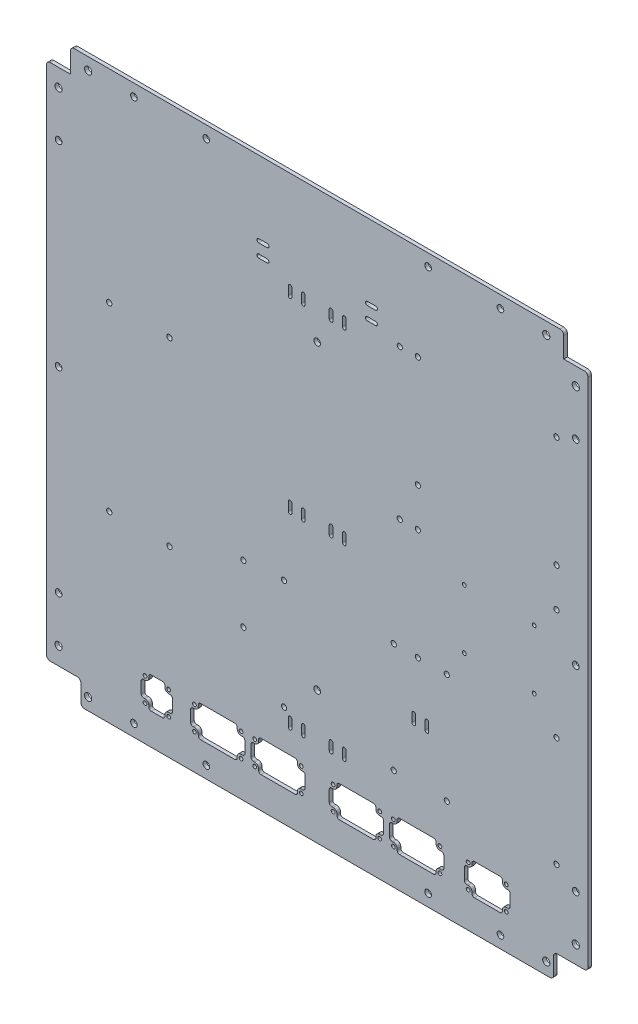
SolidWorks part; units mm, degrees
material "Acrylic (Medium-high impact)"
ref_plane "Front" through (0, 0, 0) normal (0, 0, 1) x (1, 0, 0)
ref_plane "Top" through (0, 0, 0) normal (0, 1, 0) x (1, 0, 0)
ref_plane "Right" through (0, 0, 0) normal (1, 0, 0) x (0, 0, -1)
sketch "Sketch2" plane through (0, 0, 0) normal (0, 0, 1) x (1, 0, 0)
  line L1 (0, 0) -> (449, 0)
  line L2 (0, 0) -> (0, 470)
  line L3 (0, 470) -> (449, 470)
  line L4 (449, 0) -> (449, 470)
  dimension "D1" = 449
  dimension "D2" = 470
extrude "Boss-Extrude1" add sketch "Sketch2" along normal blind 3
sketch "Sketch3" plane through (0, 0, 0) normal (0, 0, -1) x (-1, 0, 0)
  line L0 (-98.15, 52) -> (-98.15, 45.65)
  line L1 (-449, 0) -> (-429, 0)
  line L2 (-449, 0) -> (-449, 20)
  line L3 (-449, 20) -> (-429, 20)
  line L4 (-429, 0) -> (-429, 20)
  line L5 (0, 0) -> (-20, 0)
  line L6 (0, 0) -> (0, 20)
  line L7 (0, 20) -> (-20, 20)
  line L8 (-20, 0) -> (-20, 20)
  line L9 (-449, 470) -> (-429, 470)
  line L10 (-449, 470) -> (-449, 450)
  line L11 (-449, 450) -> (-429, 450)
  line L12 (-429, 470) -> (-429, 450)
  line L13 (0, 470) -> (-20, 470)
  line L14 (0, 470) -> (0, 450)
  line L15 (0, 450) -> (-20, 450)
  line L16 (-20, 470) -> (-20, 450)
  line L17 (-104.5, 26) -> (-78.5, 26) construction
  line L18 (-104.5, 26) -> (-104.5, 52) construction
  line L19 (-104.5, 52) -> (-78.5, 52) construction
  line L20 (-78.5, 26) -> (-78.5, 52) construction
  line L21 (0, 0) -> (-449, 0) construction
  line L22 (0, 470) -> (0, 0) construction
  line L23 (-98.15, 45.65) -> (-104.5, 45.65)
  line L24 (-104.5, 45.65) -> (-104.5, 32.35)
  line L25 (-104.5, 32.35) -> (-98.15, 32.35)
  line L26 (-98.15, 32.35) -> (-98.15, 26)
  line L27 (-98.15, 26) -> (-84.85, 26)
  line L28 (-84.85, 26) -> (-84.85, 32.35)
  line L29 (-84.85, 32.35) -> (-78.5, 32.35)
  line L30 (-78.5, 32.35) -> (-78.5, 45.65)
  line L31 (-78.5, 45.65) -> (-84.85, 45.65)
  line L32 (-84.85, 45.65) -> (-84.85, 52)
  line L33 (-84.85, 52) -> (-98.15, 52)
  dimension "D1" = 20
  dimension "D2" = 20
  dimension "D3" = 20
  dimension "D4" = 20
  dimension "D5" = 26
  dimension "D6" = 26
  dimension "D8" = 26
  dimension "D7" = 78.5
  dimension "D9" = 6.35
extrude "bed heater panel cutout" cut sketch "Sketch3" against normal blind 30
hole_wizard "M5 Clearance Hole1" positions "Sketch4" profile "Sketch5" hole size "M5" standard "ANSI Metric" end condition up to next
sketch "Sketch4" plane through (0, 0, 0) normal (0, 0, -1) x (-1, 0, 0)
  line L0 (-224.5, 470) -> (-224.5, 0) construction
  line L1 (-429, 470) -> (-20, 470) construction
  line L2 (-20, 0) -> (-429, 0) construction
  line L3 (-429, 460) -> (-376.5, 460) construction
  line L5 (-429, 450) -> (-429, 470) construction
  line L6 (-376.5, 460) -> (-72.5, 460) construction
  line L7 (-72.5, 460) -> (-20, 460) construction
  line L8 (-20, 470) -> (-20, 450) construction
  line L9 (-449, 235) -> (0, 235) construction
  line L10 (-449, 20) -> (-449, 450) construction
  line L12 (0, 450) -> (0, 20) construction
  line L13 (-439, 450) -> (-439, 20) construction
  line L14 (-449, 450) -> (-429, 450) construction
  line L15 (-429, 20) -> (-449, 20) construction
  line L18 (-10, 450) -> (-10, 20) construction
  line L19 (-20, 450) -> (0, 450) construction
  line L20 (0, 20) -> (-20, 20) construction
  line L21 (-429, 10) -> (-20, 10) construction
  line L22 (-429, 0) -> (-429, 20) construction
  line L23 (-20, 20) -> (-20, 0) construction
  point P13 (-224.5, 360)
  point P17 (-224.5, 110)
  point P24 (-376.5, 460)
  point P29 (-72.5, 460)
  point P54 (-316.5, 460)
  point P56 (-132.5, 460)
  point P59 (-72.5, 10)
  point P60 (-132.5, 10)
  point P61 (-316.5, 10)
  point P62 (-376.5, 10)
  point P83 (-439, 397.5)
  point P85 (-439, 72.5)
  point P92 (-10, 72.5)
  point P93 (-10, 397.5)
  point P97 (-439, 235)
  point P103 (-10, 235)
  point P126 (-20, 460)
  dimension "D5" = 52.5
  dimension "D8" = 52.5
  dimension "D9" = 52.5
  dimension "D3" = 100
  dimension "D2" = 100
  dimension "D1" = 60
  dimension "D4" = 60
sketch "Sketch5" plane through (10, 235, 0) normal (1, 0, 0) x (0, 1, 0)
  line L0 (0, 0) -> (0, 3)
  line L1 (0, 3) -> (2.75, 3)
  line L2 (2.75, 3) -> (2.75, 0)
  line L5 (2.75, 0) -> (0, 0)
  line L11 (0, -6.35) -> (0, 107.95) construction
  dimension "Thru Hole Dia." = 5.5
  dimension "Thru Hole Depth" = 3
sketch "Sketch10" plane through (0, 0, 0) normal (0, 0, -1) x (-1, 0, 0)
  line L0 (-20, 20) -> (-429, 20) construction
  line L1 (-164.5, 26) -> (-119.5, 26) construction
  line L2 (-164.5, 26) -> (-164.5, 52) construction
  line L3 (-164.5, 52) -> (-119.5, 52) construction
  line L4 (-119.5, 26) -> (-119.5, 52) construction
  line L5 (-429, 0) -> (-429, 20) construction
  line L6 (-429, 20) -> (-449, 20) construction
  line L7 (-224.5, 20) -> (-224.5, 145.1565) construction
  line L8 (-158.15, 52) -> (-158.15, 45.65)
  line L15 (-169.5, 52) -> (-214.5, 52) construction
  line L16 (-169.5, 52) -> (-169.5, 26) construction
  line L17 (-169.5, 26) -> (-214.5, 26) construction
  line L18 (-214.5, 52) -> (-214.5, 26) construction
  line L22 (-158.15, 45.65) -> (-164.5, 45.65)
  line L23 (-164.5, 45.65) -> (-164.5, 32.35)
  line L24 (-164.5, 32.35) -> (-158.15, 32.35)
  line L25 (-158.15, 32.35) -> (-158.15, 26)
  line L26 (-158.15, 26) -> (-125.85, 26)
  line L27 (-125.85, 26) -> (-125.85, 32.35)
  line L28 (-125.85, 32.35) -> (-119.5, 32.35)
  line L29 (-119.5, 32.35) -> (-119.5, 45.65)
  line L30 (-119.5, 45.65) -> (-125.85, 45.65)
  line L31 (-125.85, 45.65) -> (-125.85, 52)
  line L32 (-125.85, 52) -> (-158.15, 52)
  line L33 (-208.15, 52) -> (-208.15, 45.65)
  line L34 (-208.15, 45.65) -> (-214.5, 45.65)
  line L35 (-214.5, 45.65) -> (-214.5, 32.35)
  line L36 (-214.5, 32.35) -> (-208.15, 32.35)
  line L37 (-208.15, 32.35) -> (-208.15, 26)
  line L38 (-208.15, 26) -> (-175.85, 26)
  line L39 (-175.85, 26) -> (-175.85, 32.35)
  line L40 (-175.85, 32.35) -> (-169.5, 32.35)
  line L41 (-169.5, 32.35) -> (-169.5, 45.65)
  line L42 (-169.5, 45.65) -> (-175.85, 45.65)
  line L43 (-175.85, 45.65) -> (-175.85, 52)
  line L44 (-175.85, 52) -> (-208.15, 52)
  line L45 (-234.5, 52) -> (-234.5, 26) construction
  line L46 (-279.5, 26) -> (-234.5, 26) construction
  line L47 (-279.5, 52) -> (-279.5, 26) construction
  line L48 (-279.5, 52) -> (-234.5, 52) construction
  line L49 (-329.5, 26) -> (-329.5, 52) construction
  line L50 (-284.5, 52) -> (-329.5, 52) construction
  line L51 (-284.5, 26) -> (-284.5, 52) construction
  line L52 (-284.5, 26) -> (-329.5, 26) construction
  line L53 (-273.15, 52) -> (-240.85, 52)
  line L54 (-273.15, 45.65) -> (-273.15, 52)
  line L55 (-279.5, 45.65) -> (-273.15, 45.65)
  line L56 (-279.5, 32.35) -> (-279.5, 45.65)
  line L57 (-273.15, 32.35) -> (-279.5, 32.35)
  line L58 (-273.15, 26) -> (-273.15, 32.35)
  line L59 (-240.85, 26) -> (-273.15, 26)
  line L60 (-240.85, 32.35) -> (-240.85, 26)
  line L61 (-234.5, 32.35) -> (-240.85, 32.35)
  line L62 (-234.5, 45.65) -> (-234.5, 32.35)
  line L63 (-240.85, 45.65) -> (-234.5, 45.65)
  line L64 (-240.85, 52) -> (-240.85, 45.65)
  line L65 (-323.15, 52) -> (-290.85, 52)
  line L66 (-323.15, 45.65) -> (-323.15, 52)
  line L67 (-329.5, 45.65) -> (-323.15, 45.65)
  line L68 (-329.5, 32.35) -> (-329.5, 45.65)
  line L69 (-323.15, 32.35) -> (-329.5, 32.35)
  line L70 (-323.15, 26) -> (-323.15, 32.35)
  line L71 (-290.85, 26) -> (-323.15, 26)
  line L72 (-290.85, 32.35) -> (-290.85, 26)
  line L73 (-284.5, 32.35) -> (-290.85, 32.35)
  line L74 (-284.5, 45.65) -> (-284.5, 32.35)
  line L75 (-290.85, 45.65) -> (-284.5, 45.65)
  line L76 (-290.85, 52) -> (-290.85, 45.65)
  line L77 (-20, 0) -> (-429, 0) construction
  dimension "D1" = 6.35
  dimension "D2" = 45
  dimension "D3" = 10
  dimension "D4" = 26
  dimension "D5" = 5
  dimension "D6" = 26
extrude "extruder panel cutouts" cut sketch "Sketch10" against normal through all
sketch "Sketch16" plane through (0, 0, 0) normal (0, 0, -1) x (-1, 0, 0)
  line L0 (-323.15, 26) -> (-290.85, 26) construction
  line L1 (-346.5, 26) -> (-384.5, 26) construction
  line L2 (-346.5, 26) -> (-346.5, 52) construction
  line L3 (-346.5, 52) -> (-384.5, 52) construction
  line L4 (-384.5, 26) -> (-384.5, 52) construction
  line L6 (-378.15, 52) -> (-378.15, 45.65)
  line L7 (-378.15, 45.65) -> (-384.5, 45.65)
  line L8 (-384.5, 45.65) -> (-384.5, 32.35)
  line L9 (-384.5, 32.35) -> (-378.15, 32.35)
  line L10 (-378.15, 32.35) -> (-378.15, 26)
  line L11 (-378.15, 26) -> (-352.85, 26)
  line L12 (-352.85, 26) -> (-352.85, 32.35)
  line L13 (-352.85, 32.35) -> (-346.5, 32.35)
  line L14 (-346.5, 32.35) -> (-346.5, 45.65)
  line L15 (-346.5, 45.65) -> (-352.85, 45.65)
  line L16 (-352.85, 45.65) -> (-352.85, 52)
  line L17 (-352.85, 52) -> (-378.15, 52)
  line L18 (-449, 20) -> (-449, 450) construction
  dimension "D1" = 26
  dimension "D2" = 38
  dimension "D3" = 64.5
  dimension "D4" = 6.35
extrude "z_motor_panel_cutout" cut sketch "Sketch16" against normal blind 10
fillet "Fillet1" radius 3.175 24 edges at (125.85, 45.65, 1.5) (125.85, 32.35, 1.5) (158.15, 32.35, 1.5) (158.15, 45.65, 1.5) (208.15, 32.35, 1.5) (208.15, 45.65, 1.5) (175.85, 32.35, 1.5) (175.85, 45.65, 1.5) (323.15, 45.65, 1.5) (323.15, 32.35, 1.5) (290.85, 32.35, 1.5) (290.85, 45.65, 1.5) (273.15, 32.35, 1.5) (273.15, 45.65, 1.5) (240.85, 32.35, 1.5) (240.85, 45.65, 1.5) (378.15, 32.35, 1.5) (352.85, 45.65, 1.5) (352.85, 32.35, 1.5) (378.15, 45.65, 1.5) (84.85, 45.65, 1.5) (84.85, 32.35, 1.5) (98.15, 32.35, 1.5) (98.15, 45.65, 1.5)
sketch "Sketch17" plane through (0, 0, 0) normal (0, 0, -1) x (-1, 0, 0)
  circle A0 centre (-381.325, 48.825) radius 1.55
  circle A1 centre (-349.675, 48.825) radius 1.55
  circle A2 centre (-349.675, 29.175) radius 1.55
  circle A3 centre (-381.325, 29.175) radius 1.55
  circle A4 centre (-326.325, 48.825) radius 1.55
  circle A5 centre (-287.675, 48.825) radius 1.55
  circle A6 centre (-287.675, 29.175) radius 1.55
  circle A7 centre (-326.325, 29.175) radius 1.55
  circle A8 centre (-276.325, 48.825) radius 1.55
  circle A9 centre (-237.675, 48.825) radius 1.55
  circle A10 centre (-237.675, 29.175) radius 1.55
  circle A11 centre (-276.325, 29.175) radius 1.55
  circle A12 centre (-211.325, 48.825) radius 1.55
  circle A13 centre (-172.675, 48.825) radius 1.55
  circle A14 centre (-172.675, 29.175) radius 1.55
  circle A15 centre (-211.325, 29.175) radius 1.55
  circle A16 centre (-161.325, 48.825) radius 1.55
  circle A17 centre (-122.675, 48.825) radius 1.55
  circle A18 centre (-122.675, 29.175) radius 1.55
  circle A19 centre (-161.325, 29.175) radius 1.55
  circle A20 centre (-101.325, 48.825) radius 1.55
  circle A21 centre (-81.675, 48.825) radius 1.55
  circle A22 centre (-101.325, 29.175) radius 1.55
  circle A23 centre (-81.675, 29.175) radius 1.55
  dimension "D1" = 3.1
extrude "Cut-Extrude3" cut sketch "Sketch17" against normal through all
sketch "Sketch7" plane through (0, 0, 0) normal (0, 0, -1) x (-1, 0, 0)
  line L0 (-449, 20) -> (-449, 450) construction
  line L1 (-423, 299) -> (-308, 299) construction
  line L2 (-423, 299) -> (-423, 391) construction
  line L3 (-423, 391) -> (-308, 391) construction
  line L4 (-308, 299) -> (-308, 391) construction
  line L5 (-423, 299) -> (-308, 391) construction
  line L6 (-423, 391) -> (-308, 299) construction
  line L7 (-304, 295) -> (-427, 295) construction
  line L8 (-304, 295) -> (-304, 395) construction
  line L9 (-304, 395) -> (-427, 395) construction
  line L10 (-427, 295) -> (-427, 395) construction
  line L11 (-304, 295) -> (-427, 395) construction
  line L12 (-304, 395) -> (-427, 295) construction
  line L13 (-449, 450) -> (-429, 450) construction
  line L14 (-423, 175) -> (-308, 175) construction
  line L15 (-423, 175) -> (-423, 267) construction
  line L16 (-423, 267) -> (-308, 267) construction
  line L17 (-308, 175) -> (-308, 267) construction
  line L18 (-423, 175) -> (-308, 267) construction
  line L19 (-423, 267) -> (-308, 175) construction
  line L20 (-304, 171) -> (-427, 171) construction
  line L21 (-304, 171) -> (-304, 271) construction
  line L22 (-304, 271) -> (-427, 271) construction
  line L23 (-427, 171) -> (-427, 271) construction
  line L24 (-304, 171) -> (-427, 271) construction
  line L25 (-304, 271) -> (-427, 171) construction
  circle A0 centre (-423, 391) radius 2.15
  circle A1 centre (-308, 391) radius 2.15
  circle A2 centre (-308, 299) radius 2.15
  circle A3 centre (-423, 299) radius 2.15
  circle A4 centre (-423, 267) radius 2.15
  circle A5 centre (-308, 267) radius 2.15
  circle A6 centre (-308, 175) radius 2.15
  circle A7 centre (-423, 175) radius 2.15
  point P0 (-365.5, 345)
  point P6 (-365.5, 345)
  point P19 (-365.5, 221)
  point P25 (-365.5, 221)
  dimension "D5" = 4.3
  dimension "D12" = 4.3
  dimension "D1" = 115
  dimension "D2" = 92
  dimension "D3" = 123
  dimension "D4" = 100
  dimension "D6" = 22
  dimension "D7" = 55
  dimension "D8" = 115
  dimension "D9" = 92
  dimension "D10" = 123
  dimension "D11" = 100
  dimension "D13" = 24
extrude "Duet2 mounting holes" cut sketch "Sketch7" against normal through all
sketch "Sketch9" plane through (0, 0, 0) normal (0, 0, -1) x (-1, 0, 0)
  line L0 (0, 450) -> (0, 20) construction
  line L1 (-102, 152) -> (-52, 152) construction
  line L2 (-102, 152) -> (-102, 302) construction
  line L3 (-102, 302) -> (-52, 302) construction
  line L4 (-52, 152) -> (-52, 302) construction
  line L5 (-102, 152) -> (-52, 302) construction
  line L6 (-102, 302) -> (-52, 152) construction
  line L8 (-20, 0) -> (-429, 0) construction
  line L9 (-20, 120) -> (-134, 120) construction
  line L10 (-20, 120) -> (-20, 334) construction
  line L11 (-20, 334) -> (-134, 334) construction
  line L12 (-134, 120) -> (-134, 334) construction
  line L13 (-20, 120) -> (-134, 334) construction
  line L14 (-20, 334) -> (-134, 120) construction
  circle A0 centre (-52, 302) radius 2.2
  circle A1 centre (-102, 302) radius 2.2
  circle A2 centre (-52, 152) radius 2.2
  circle A3 centre (-102, 152) radius 2.2
  point P0 (-77, 227)
  point P11 (-77, 227)
  point P21 (-77, 302)
  dimension "D1" = 50
  dimension "D3" = 4.4
  dimension "D2" = 114
  dimension "D4" = 32
  dimension "D5" = 150
  dimension "D6" = 20
  dimension "D7" = 120
extrude "psu mounting holes" cut sketch "Sketch9" against normal through all
sketch "Sketch11" plane through (0, 0, 0) normal (0, 0, -1) x (-1, 0, 0)
  line L0 (-224.5, 0) -> (-224.5, 150.8562) construction
  line L1 (-20, 0) -> (-429, 0) construction
  line L2 (-163.25, 124.6) -> (-163.25, 172.6) construction
  circle A0 centre (-163.25, 172.6) radius 2.15
  circle A1 centre (-163.25, 124.6) radius 2.15
  dimension "D1" = 48
  dimension "D2" = 4.3
  dimension "D3" = 124.6
  dimension "D4" = 61.25
extrude "ssr holes" cut sketch "Sketch11" against normal through all
sketch "Sketch18" plane through (0, 0, 0) normal (0, 0, -1) x (-1, 0, 0)
  line L0 (-423, 267) -> (-293, 267) construction
  line L1 (-423, 391) -> (-293, 391) construction
  line L2 (-428, 396) -> (-288, 396) construction
  line L3 (-423, 391) -> (-293, 391) construction
  line L4 (-423, 391) -> (-423, 267) construction
  line L5 (-423, 267) -> (-293, 267) construction
  line L6 (-293, 391) -> (-293, 267) construction
  line L7 (-288, 396) -> (-288, 262) construction
  line L8 (-428, 262) -> (-288, 262) construction
  line L9 (-428, 396) -> (-428, 262) construction
  line L10 (-404.5, 246.5) -> (-346.5, 246.5) construction
  line L11 (-428, 250) -> (-343, 250) construction
  line L12 (-428, 250) -> (-428, 194) construction
  line L13 (-428, 194) -> (-343, 194) construction
  line L14 (-343, 250) -> (-343, 194) construction
  line L15 (-346.5, 246.5) -> (-346.5, 197.5) construction
  line L16 (-346.5, 197.5) -> (-404.5, 197.5) construction
  line L17 (-404.5, 197.5) -> (-404.5, 246.5) construction
  line L18 (-423, 84) -> (-423, 175) construction
  line L19 (-427.5, 79.5) -> (-327.5, 79.5) construction
  line L20 (-427.5, 79.5) -> (-427.5, 179.5) construction
  line L21 (-427.5, 179.5) -> (-327.5, 179.5) construction
  line L22 (-327.5, 79.5) -> (-327.5, 179.5) construction
  line L23 (-423, 175) -> (-332, 175) construction
  line L24 (-332, 84) -> (-332, 175) construction
  line L25 (-423, 84) -> (-332, 84) construction
  line L26 (-192.5, 179.5) -> (-292.5, 179.5) construction
  line L27 (-197, 175) -> (-288, 175) construction
  line L28 (-197, 175) -> (-197, 84) construction
  line L29 (-197, 84) -> (-288, 84) construction
  line L30 (-288, 175) -> (-288, 84) construction
  line L31 (-292.5, 179.5) -> (-292.5, 79.5) construction
  line L32 (-192.5, 79.5) -> (-292.5, 79.5) construction
  line L33 (-192.5, 179.5) -> (-192.5, 79.5) construction
  circle A0 centre (-293, 391) radius 2.15
  circle A1 centre (-423, 391) radius 2.15 construction
  circle A2 centre (-293, 267) radius 2.15
  circle A3 centre (-404.5, 246.5) radius 1.6
  circle A4 centre (-346.5, 246.5) radius 1.6
  circle A5 centre (-346.5, 197.5) radius 1.6
  circle A6 centre (-404.5, 197.5) radius 1.6
  circle A7 centre (-332, 175) radius 2.15
  circle A8 centre (-332, 84) radius 2.15
  circle A9 centre (-423, 84) radius 2.15
  circle A10 centre (-423, 175) radius 2.15 construction
  circle A11 centre (-288, 175) radius 2.15
  circle A12 centre (-288, 84) radius 2.15
  circle A13 centre (-197, 84) radius 2.15
  circle A14 centre (-163.25, 172.6) radius 2.15 construction
  circle A15 centre (-197, 175) radius 2.15
  dimension "D2" = 4.3
  dimension "D11" = 3.2
  dimension "D1" = 130
  dimension "D3" = 124
  dimension "D5" = 85
  dimension "D6" = 56
  dimension "D8" = 3.5
  dimension "D9" = 3.5
  dimension "D10" = 58
  dimension "D12" = 12
  dimension "D7" = 3.5
  dimension "D14" = 100
  dimension "D16" = 91
  dimension "D13" = 14.5
  dimension "D17" = 91
  dimension "D19" = 35
  dimension "D4" = 5
  dimension "D15" = 4.5
  dimension "D18" = 4.5
extrude "Duet3, Expanders, and Raspi Holes" cut sketch "Sketch18" against normal through all
sketch "Sketch12" plane through (0, 0, 0) normal (0, 0, -1) x (-1, 0, 0)
  line L0 (-414.5, 460) -> (-429, 460) construction
  line L1 (-429, 450) -> (-429, 470) construction
  line L2 (-20, 460) -> (-34.5, 460) construction
  line L3 (-20, 470) -> (-20, 450) construction
  line L4 (-439, 450) -> (-439, 435.5) construction
  line L5 (-449, 450) -> (-429, 450) construction
  line L6 (-439, 20) -> (-439, 34.5) construction
  line L7 (-429, 20) -> (-449, 20) construction
  line L8 (-429, 10) -> (-414.5, 10) construction
  line L9 (-429, 0) -> (-429, 20) construction
  line L10 (-20, 10) -> (-34.5, 10) construction
  line L11 (-20, 20) -> (-20, 0) construction
  line L12 (-10, 20) -> (-10, 34.5) construction
  line L13 (0, 20) -> (-20, 20) construction
  line L14 (-10, 450) -> (-10, 435.5) construction
  line L15 (-20, 450) -> (0, 450) construction
  circle A0 centre (-414.5, 460) radius 3
  circle A1 centre (-34.5, 460) radius 3
  circle A2 centre (-439, 435.5) radius 3
  circle A3 centre (-439, 34.5) radius 3
  circle A4 centre (-414.5, 10) radius 3
  circle A5 centre (-34.5, 10) radius 3
  circle A6 centre (-10, 34.5) radius 3
  circle A7 centre (-10, 435.5) radius 3
  dimension "D1" = 14.5
  dimension "D2" = 6
extrude "inside corner bracket screw clearance holes" cut sketch "Sketch12" against normal through all
sketch "Sketch6" plane through (0, 0, 0) normal (0, 0, -1) x (-1, 0, 0)
  line L0 (-224.5, 470) -> (-224.5, 0) construction
  line L1 (-429, 470) -> (-20, 470) construction
  line L2 (-20, 0) -> (-429, 0) construction
  line L3 (-234.5, 470) -> (-234.5, 0) construction
  line L4 (-429, 450) -> (-20, 450) construction
  line L5 (-245.5, 235) -> (-245.5, 225)
  line L6 (-234.5, 390) -> (-237.5, 390)
  line L7 (-234.5, 390) -> (-234.5, 380)
  line L8 (-234.5, 380) -> (-237.5, 380)
  line L9 (-237.5, 390) -> (-237.5, 380)
  line L10 (-245.5, 390) -> (-248.5, 390)
  line L11 (-245.5, 390) -> (-245.5, 380)
  line L12 (-245.5, 380) -> (-248.5, 380)
  line L13 (-248.5, 390) -> (-248.5, 380)
  line L14 (-245.5, 235) -> (-248.5, 235)
  line L15 (-248.5, 235) -> (-248.5, 225)
  line L16 (-245.5, 225) -> (-248.5, 225)
  line L17 (-234.5, 235) -> (-234.5, 225)
  line L18 (-234.5, 235) -> (-237.5, 235)
  line L19 (-237.5, 235) -> (-237.5, 225)
  line L20 (-234.5, 225) -> (-237.5, 225)
  line L69 (-214.5, 225) -> (-211.5, 225)
  line L70 (-211.5, 235) -> (-211.5, 225)
  line L71 (-214.5, 235) -> (-211.5, 235)
  line L72 (-214.5, 235) -> (-214.5, 225)
  line L73 (-203.5, 225) -> (-200.5, 225)
  line L74 (-200.5, 235) -> (-200.5, 225)
  line L75 (-203.5, 235) -> (-200.5, 235)
  line L76 (-200.5, 390) -> (-200.5, 380)
  line L77 (-203.5, 380) -> (-200.5, 380)
  line L78 (-203.5, 390) -> (-203.5, 380)
  line L79 (-203.5, 390) -> (-200.5, 390)
  line L80 (-211.5, 390) -> (-211.5, 380)
  line L81 (-214.5, 380) -> (-211.5, 380)
  line L82 (-214.5, 390) -> (-214.5, 380)
  line L83 (-214.5, 390) -> (-211.5, 390)
  line L84 (-203.5, 235) -> (-203.5, 225)
  line L85 (-245.5, 80) -> (-245.5, 70)
  line L86 (-245.5, 70) -> (-248.5, 70)
  line L87 (-248.5, 80) -> (-248.5, 70)
  line L88 (-245.5, 80) -> (-248.5, 80)
  line L89 (-234.5, 80) -> (-234.5, 70)
  line L90 (-234.5, 70) -> (-237.5, 70)
  line L91 (-237.5, 80) -> (-237.5, 70)
  line L92 (-234.5, 80) -> (-237.5, 80)
  line L93 (-214.5, 70) -> (-211.5, 70)
  line L98 (-211.5, 80) -> (-211.5, 70)
  line L99 (-214.5, 80) -> (-211.5, 80)
  line L104 (-214.5, 80) -> (-214.5, 70)
  line L105 (-174.5, 407) -> (-174.5, 410)
  line L106 (-274.5, 396) -> (-264.5, 396)
  line L107 (-274.5, 396) -> (-274.5, 399)
  line L108 (-274.5, 399) -> (-264.5, 399)
  line L109 (-264.5, 396) -> (-264.5, 399)
  line L110 (-264.5, 407) -> (-274.5, 407)
  line L111 (-264.5, 407) -> (-264.5, 410)
  line L112 (-264.5, 410) -> (-274.5, 410)
  line L113 (-274.5, 407) -> (-274.5, 410)
  line L114 (-184.5, 410) -> (-174.5, 410)
  line L115 (-184.5, 407) -> (-184.5, 410)
  line L116 (-184.5, 407) -> (-174.5, 407)
  line L117 (-184.5, 396) -> (-184.5, 399)
  line L118 (-174.5, 399) -> (-184.5, 399)
  line L119 (-174.5, 396) -> (-174.5, 399)
  line L120 (-174.5, 396) -> (-184.5, 396)
  line L121 (-245.5, 80) -> (-245.5, 70) [skipped]
  line L122 (-245.5, 80) -> (-248.5, 80) [skipped]
  line L123 (-248.5, 80) -> (-248.5, 70) [skipped]
  line L124 (-245.5, 70) -> (-248.5, 70) [skipped]
  line L125 (-234.5, 80) -> (-234.5, 70) [skipped]
  line L126 (-234.5, 80) -> (-237.5, 80) [skipped]
  line L127 (-237.5, 80) -> (-237.5, 70) [skipped]
  line L128 (-234.5, 70) -> (-237.5, 70) [skipped]
  line L129 (-203.5, 70) -> (-200.5, 70)
  line L130 (-200.5, 80) -> (-200.5, 70)
  line L131 (-203.5, 80) -> (-200.5, 80)
  line L132 (-203.5, 80) -> (-203.5, 70)
  line L133 (-315.5, 129.5) -> (-327.5, 129.5) construction
  line L136 (-327.5, 79.5) -> (-327.5, 179.5) construction
  line L137 (-317, 124.5) -> (-314, 124.5)
  line L138 (-317, 124.5) -> (-317, 134.5)
  line L139 (-317, 134.5) -> (-314, 134.5)
  line L140 (-314, 124.5) -> (-314, 134.5)
  line L141 (-317, 124.5) -> (-314, 134.5) construction
  line L142 (-317, 134.5) -> (-314, 124.5) construction
  line L143 (-306, 124.5) -> (-303, 124.5)
  line L144 (-306, 124.5) -> (-306, 134.5)
  line L145 (-306, 134.5) -> (-303, 134.5)
  line L146 (-303, 124.5) -> (-303, 134.5)
  line L147 (-306, 124.5) -> (-303, 134.5) construction
  line L148 (-306, 134.5) -> (-303, 124.5) construction
  line L149 (-315.5, 129.5) -> (-304.5, 129.5) construction
  line L150 (-304.5, 129.5) -> (-292.5, 129.5) construction
  line L151 (-292.5, 179.5) -> (-292.5, 79.5) construction
  point P80 (-305.4583, 129.5)
  point P82 (-315.5, 129.5)
  point P87 (-304.5, 129.5)
  point P111 (-300.8111, 124.5)
  dimension "D1" = 10
  dimension "D3" = 3
  dimension "D4" = 8
  dimension "D6" = 60
  dimension "D11" = 8
  dimension "D12" = 60
  dimension "D13" = 40
  dimension "D7" = 155
  dimension "D9" = 155
  dimension "D10" = 8
extrude "main wiring tie-downs" cut sketch "Sketch6" against normal through all
sketch "Sketch13" plane through (0, 0, 0) normal (0, 0, -1) x (-1, 0, 0)
  line L0 (-429, 0) -> (-429, 20) construction
  line L1 (-429, 0) -> (-420.5, 0)
  line L2 (-429, 0) -> (-429, 20)
  line L3 (-429, 20) -> (-420.5, 20)
  line L4 (-420.5, 0) -> (-420.5, 20)
  line L5 (-20, 0) -> (-28.5, 0)
  line L6 (-20, 0) -> (-20, 20)
  line L7 (-20, 20) -> (-28.5, 20)
  line L8 (-28.5, 0) -> (-28.5, 20)
  line L9 (-429, 20) -> (-449, 20) construction
  dimension "D1" = 8.5
extrude "Cut-Extrude1" cut sketch "Sketch13" against normal through all
fillet "Fillet2" radius 3 10 edges at (20, 470, 1.5) (0, 450, 1.5) (449, 450, 1.5) (429, 470, 1.5) (0, 20, 1.5) (28.5, 20, 1.5) (28.5, 0, 1.5) (449, 20, 1.5) (420.5, 20, 1.5) (420.5, 0, 1.5)
fillet "Fillet3" radius 2 48 edges at (98.15, 52, 1.5) (104.5, 45.65, 1.5) (104.5, 32.35, 1.5) (98.15, 26, 1.5) (84.85, 26, 1.5) (78.5, 32.35, 1.5) (84.85, 52, 1.5) (78.5, 45.65, 1.5) (119.5, 45.65, 1.5) (125.85, 52, 1.5) (125.85, 26, 1.5) (119.5, 32.35, 1.5) (164.5, 32.35, 1.5) (158.15, 26, 1.5) (164.5, 45.65, 1.5) (158.15, 52, 1.5) (175.85, 52, 1.5) (169.5, 45.65, 1.5) (214.5, 45.65, 1.5) (208.15, 52, 1.5) (214.5, 32.35, 1.5) (208.15, 26, 1.5) (169.5, 32.35, 1.5) (175.85, 26, 1.5) (234.5, 32.35, 1.5) (240.85, 26, 1.5) (234.5, 45.65, 1.5) (240.85, 52, 1.5) (273.15, 52, 1.5) (279.5, 45.65, 1.5) (273.15, 26, 1.5) (279.5, 32.35, 1.5) (290.85, 52, 1.5) (284.5, 45.65, 1.5) (323.15, 52, 1.5) (329.5, 45.65, 1.5) (329.5, 32.35, 1.5) (323.15, 26, 1.5) (284.5, 32.35, 1.5) (290.85, 26, 1.5) (352.85, 26, 1.5) (378.15, 26, 1.5) (384.5, 32.35, 1.5) (346.5, 32.35, 1.5) (346.5, 45.65, 1.5) (352.85, 52, 1.5) (384.5, 45.65, 1.5) (378.15, 52, 1.5)
fillet "Fillet4" radius 1.5 72 edges at (200.5, 225, 1.5) (211.5, 225, 1.5) (234.5, 225, 1.5) (245.5, 225, 1.5) (248.5, 225, 1.5) (237.5, 225, 1.5) (214.5, 225, 1.5) (203.5, 225, 1.5) (203.5, 235, 1.5) (214.5, 235, 1.5) (237.5, 235, 1.5) (248.5, 235, 1.5) (245.5, 235, 1.5) (234.5, 235, 1.5) (211.5, 235, 1.5) (200.5, 235, 1.5) (264.5, 399, 1.5) (264.5, 410, 1.5) (274.5, 407, 1.5) (274.5, 396, 1.5) (274.5, 399, 1.5) (274.5, 410, 1.5) (264.5, 396, 1.5) (264.5, 407, 1.5) (245.5, 380, 1.5) (234.5, 380, 1.5) (237.5, 380, 1.5) (248.5, 380, 1.5) (234.5, 390, 1.5) (245.5, 390, 1.5) (237.5, 390, 1.5) (248.5, 390, 1.5) (214.5, 390, 1.5) (211.5, 390, 1.5) (211.5, 380, 1.5) (214.5, 380, 1.5) (203.5, 380, 1.5) (203.5, 390, 1.5) (200.5, 390, 1.5) (200.5, 380, 1.5) (174.5, 396, 1.5) (174.5, 399, 1.5) (184.5, 399, 1.5) (184.5, 396, 1.5) (184.5, 407, 1.5) (174.5, 407, 1.5) (174.5, 410, 1.5) (184.5, 410, 1.5) (214.5, 70, 1.5) (211.5, 70, 1.5) (214.5, 80, 1.5) (211.5, 80, 1.5) (200.5, 80, 1.5) (203.5, 80, 1.5) (203.5, 70, 1.5) (200.5, 70, 1.5) (245.5, 70, 1.5) (248.5, 70, 1.5) (248.5, 80, 1.5) (245.5, 80, 1.5) (237.5, 70, 1.5) (234.5, 70, 1.5) (237.5, 80, 1.5) (234.5, 80, 1.5) (317, 134.5, 1.5) (314, 134.5, 1.5) (306, 134.5, 1.5) (303, 134.5, 1.5) (317, 124.5, 1.5) (314, 124.5, 1.5) (306, 124.5, 1.5) (303, 124.5, 1.5)
other "Move Face1" [suppressed] offset 0.0762 parameters "D1"=0.0762
equation "\"D4@Sketch3\"=\"D1@Sketch3\""
equation "\"D8@Sketch4\"=\"D5@Sketch4\""
equation "\"D9@Sketch4\"=\"D8@Sketch4\""
equation "\"D2@Sketch4\"=\"D3@Sketch4\""
equation "\"D11@Sketch6\"=\"D4@Sketch6\""
equation "\"D4@Sketch4\"=\"D1@Sketch4\""
equation "\"D9@Sketch18\"=\"D8@Sketch18\""
equation "\"D17@Sketch18\"=\"D16@Sketch18\""
equation "\"D18@Sketch18\"=\"D15@Sketch18\""
equation "\"D10@Sketch6\"=\"D4@Sketch6\""
